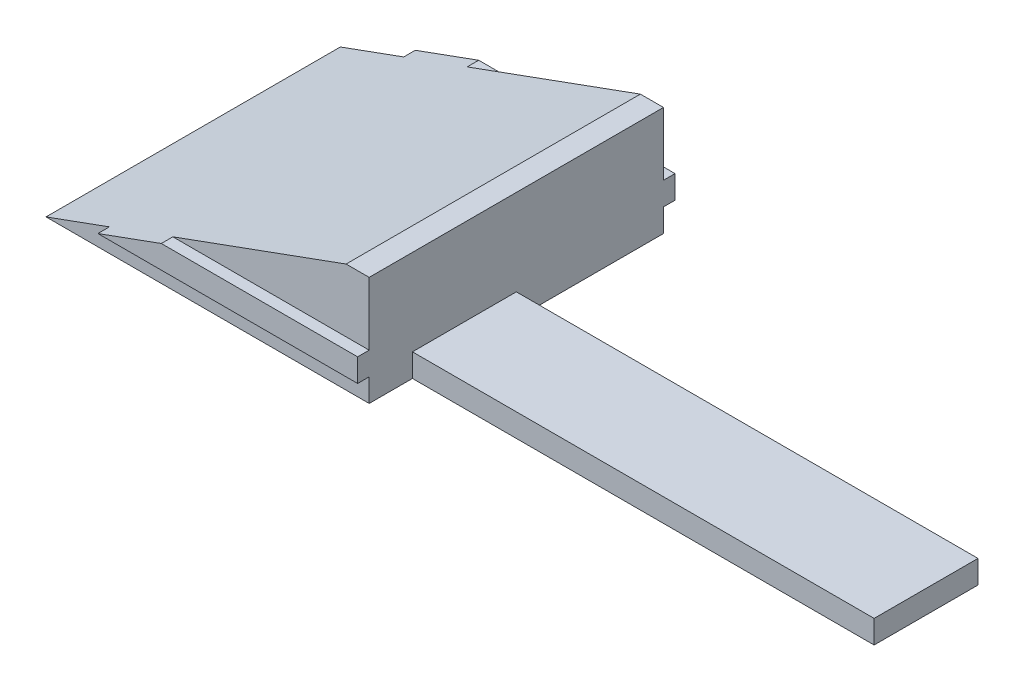
SolidWorks part; units mm, degrees
ref_plane "Front Plane" through (0, 0, 0) normal (0, 0, 1) x (1, 0, 0)
ref_plane "Top Plane" through (0, 0, 0) normal (0, 1, 0) x (1, 0, 0)
ref_plane "Right Plane" through (0, 0, 0) normal (1, 0, 0) x (0, 0, -1)
sketch "Sketch1" plane through (0, 0, 0) normal (0, 1, 0) x (1, 0, 0)
  line L1 (-13, -12.75) -> (13, -12.75)
  line L2 (-13, -12.75) -> (-13, 12.75)
  line L3 (-13, 12.75) -> (13, 12.75)
  line L4 (13, -12.75) -> (13, 12.75)
  line L5 (-13, -12.75) -> (13, 12.75) construction
  line L6 (-13, 12.75) -> (13, -12.75) construction
  point P0 (0, 0)
  dimension "D1" = 25.5
  dimension "D2" = 26
extrude "Boss-Extrude1" add sketch "Sketch1" along normal blind 9.463
sketch "Sketch2" plane through (0, 0, 12.75) normal (0, 0, 1) x (1, 0, 0)
  line L2 (-13, 9.463) -> (-13, 0) construction
  line L3 (13, 9.463) -> (13, 0) construction
  line L4 (-13, 2) -> (13, 2)
  line L5 (-13, 2) -> (-13, 4)
  line L6 (-13, 4) -> (13, 4)
  line L7 (13, 2) -> (13, 4)
extrude "Boss-Extrude3" add sketch "Sketch2" along normal blind 1
sketch "Sketch3" plane through (0, 0, -12.75) normal (0, 0, -1) x (-1, 0, 0)
  line L1 (-13, 4) -> (13, 4)
  line L2 (-13, 4) -> (-13, 2)
  line L3 (-13, 2) -> (13, 2)
  line L4 (13, 4) -> (13, 2)
extrude "Boss-Extrude4" add sketch "Sketch3" along normal blind 1
chamfer "Chamfer2" distance 9.463 angle 70 1 edges at (-13, 9.463, 0) first distance on face at (-13, 3.5772, 0)
sketch "Sketch4" plane through (13, 0, 0) normal (1, 0, 0) x (0, 0, -1)
  line L12 (-12.75, 0) -> (12.75, 0)
  line L13 (12.75, 0) -> (12.75, 2)
  line L14 (12.75, 2) -> (13.75, 2)
  line L15 (13.75, 2) -> (13.75, 4)
  line L16 (13.75, 4) -> (12.75, 4)
  line L17 (12.75, 4) -> (12.75, 9.463)
  line L18 (12.75, 9.463) -> (-12.75, 9.463)
  line L19 (-12.75, 9.463) -> (-12.75, 4)
  line L20 (-12.75, 4) -> (-13.75, 4)
  line L21 (-13.75, 4) -> (-13.75, 2)
  line L22 (-13.75, 2) -> (-12.75, 2)
  line L23 (-12.75, 2) -> (-12.75, 0)
  line L24 (-12.75, 0) -> (12.75, 0)
  line L25 (12.75, 0) -> (12.75, 2)
  line L26 (12.75, 2) -> (13.75, 2)
  line L27 (13.75, 2) -> (13.75, 4)
  line L28 (13.75, 4) -> (12.75, 4)
  line L29 (12.75, 4) -> (12.75, 9.463)
  line L30 (12.75, 9.463) -> (-12.75, 9.463)
  line L31 (-12.75, 9.463) -> (-12.75, 4)
  line L32 (-12.75, 4) -> (-13.75, 4)
  line L33 (-13.75, 4) -> (-13.75, 2)
  line L34 (-13.75, 2) -> (-12.75, 2)
  line L35 (-12.75, 2) -> (-12.75, 0)
  dimension "D1" = 0
extrude "Boss-Extrude5" add sketch "Sketch4" along normal blind 2
sketch "Sketch5" plane through (15, 0, 0) normal (1, 0, 0) x (0, 0, -1)
  line L1 (0, 0) -> (-9, 0)
  line L2 (0, 0) -> (0, 2)
  line L3 (0, 2) -> (-9, 2)
  line L4 (-9, 0) -> (-9, 2)
  dimension "D1" = 9
  dimension "D2" = 2
extrude "Boss-Extrude6" add sketch "Sketch5" along normal blind 40
